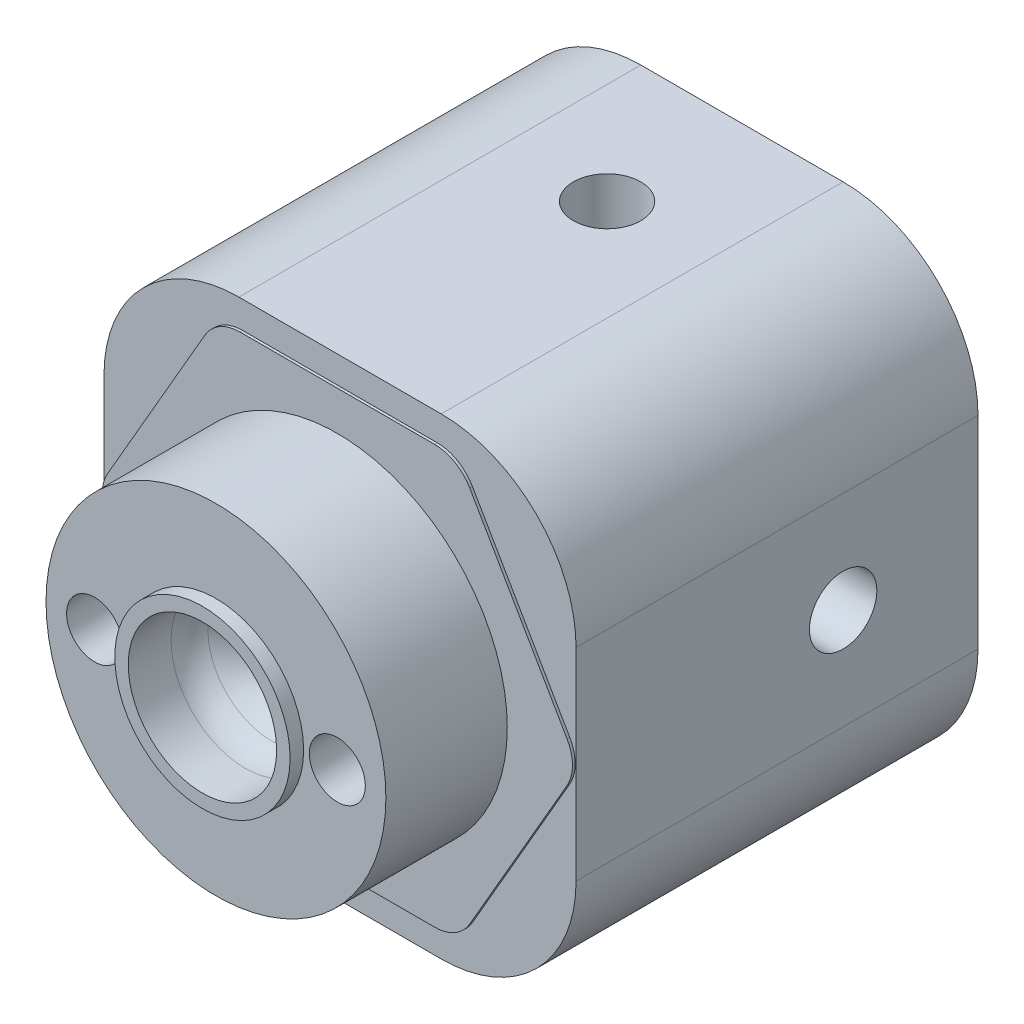
SolidWorks part; units mm, degrees
ref_plane "前视基准面" through (0, 0, 0) normal (0, 0, 1) x (1, 0, 0)
ref_plane "上视基准面" through (0, 0, 0) normal (0, 1, 0) x (1, 0, 0)
ref_plane "右视基准面" through (0, 0, 0) normal (1, 0, 0) x (0, 0, -1)
sketch "草图1" plane through (0, 0, 0) normal (0, 0, 1) x (1, 0, 0)
  circle A0 centre (0, 0) radius 12.6
  dimension "D1" = 25.2
extrude "凸台-拉伸1" add sketch "草图1" along normal blind 9
sketch "草图2" plane through (0, 0, 0) normal (0, 0, -1) x (-1, 0, 0)
  circle A0 centre (0, 0) radius 15
  dimension "D1" = 30
extrude "凸台-拉伸2" add sketch "草图2" along normal blind 5
sketch "草图3" plane through (0, 0, 9) normal (0, 0, 1) x (1, 0, 0)
  circle A0 centre (0, 0) radius 5.5
  dimension "D1" = 11
extrude "切除-拉伸1" cut sketch "草图3" against normal blind 5
sketch "草图4" plane through (0, 0, 9) normal (0, 0, 1) x (1, 0, 0)
  circle A0 centre (-9, 0) radius 2.075
  circle A1 centre (9, 0) radius 2.075
  dimension "D1" = 4.15
  dimension "D2" = 9
  dimension "D3" = 9
extrude "切除-拉伸2" cut sketch "草图4" against normal blind 29
sketch "草图5" plane through (0, 0, 4) normal (0, 0, 1) x (1, 0, 0)
  circle A0 centre (0, 0) radius 3.5
  dimension "D1" = 7
extrude "切除-拉伸3" cut sketch "草图5" against normal blind 31
fillet "圆角1" radius 3 1 edges at (5.5, 0, 4)
fillet "圆角2" radius 5 1 edges at (3.5, 0, 4)
sketch "草图6" plane through (0, 0, 9) normal (0, 0, 1) x (1, 0, 0)
  circle A0 centre (0, 0) radius 5.5
  dimension "D1" = 11
extrude "拉伸-薄壁1" add sketch "草图6" along normal blind 1 thin thin type one direction wall 1
sketch "草图7" plane through (0, 0, -5) normal (0, 0, -1) x (-1, 0, 0)
  line L1 (-8.9489, 15.5) -> (-17.8979, 0)
  line L2 (-17.8979, 0) -> (-8.9489, -15.5)
  line L3 (-8.9489, -15.5) -> (8.9489, -15.5)
  line L4 (8.9489, -15.5) -> (17.8979, 0)
  line L5 (17.8979, 0) -> (8.9489, 15.5)
  line L6 (8.9489, 15.5) -> (-8.9489, 15.5)
  circle A0 centre (0, 0) radius 15.5 construction
  circle A1 centre (0, 0) radius 15
  circle A2 centre (0, 0) radius 15
  dimension "D2" = 31
  dimension "D1" = 0
extrude "凸台-拉伸3" add sketch "草图7" against normal up to surface (5 mm away) up to face at (12.6, 0, 0)
fillet "圆角3" radius 3 6 edges at (17.8979, 0, -2.5) (8.9489, 15.5, -2.5) (-8.9489, 15.5, -2.5) (-17.8979, 0, -2.5) (-8.9489, -15.5, -2.5) (8.9489, -15.5, -2.5)
sketch "草图8" plane through (0, 0, -5) normal (0, 0, -1) x (-1, 0, 0)
  line L6 (-9.815, 14) -> (-17.0318, 1.5)
  line L7 (-17.0318, -1.5) -> (-9.815, -14)
  line L8 (-7.2169, -15.5) -> (7.2169, -15.5)
  line L9 (9.815, -14) -> (17.0318, -1.5)
  line L10 (17.0318, 1.5) -> (9.815, 14)
  line L11 (7.2169, 15.5) -> (-7.2169, 15.5)
  line L12 (-9.815, 14) -> (-17.0318, 1.5)
  line L13 (-17.0318, -1.5) -> (-9.815, -14)
  line L14 (-7.2169, -15.5) -> (7.2169, -15.5)
  line L15 (9.815, -14) -> (17.0318, -1.5)
  line L16 (17.0318, 1.5) -> (9.815, 14)
  line L17 (7.2169, 15.5) -> (-7.2169, 15.5)
  circle A0 centre (0, 0) radius 3.5 construction
  circle A1 centre (0, 0) radius 3.5
  circle A2 centre (-9, 0) radius 4
  circle A3 centre (9, 0) radius 4
  arc A6 (-17.0318, 1.5) -> (-17.0318, -1.5) centre (-14.4338, 0) ccw
  arc A7 (-9.815, -14) -> (-7.2169, -15.5) centre (-7.2169, -12.5) ccw
  arc A8 (7.2169, -15.5) -> (9.815, -14) centre (7.2169, -12.5) ccw
  arc A9 (17.0318, -1.5) -> (17.0318, 1.5) centre (14.4338, 0) ccw
  arc A10 (9.815, 14) -> (7.2169, 15.5) centre (7.2169, 12.5) ccw
  arc A11 (-7.2169, 15.5) -> (-9.815, 14) centre (-7.2169, 12.5) ccw
  arc A12 (-17.0318, 1.5) -> (-17.0318, -1.5) centre (-14.4338, 0) ccw
  arc A13 (-9.815, -14) -> (-7.2169, -15.5) centre (-7.2169, -12.5) ccw
  arc A14 (7.2169, -15.5) -> (9.815, -14) centre (7.2169, -12.5) ccw
  arc A15 (17.0318, -1.5) -> (17.0318, 1.5) centre (14.4338, 0) ccw
  arc A16 (9.815, 14) -> (7.2169, 15.5) centre (7.2169, 12.5) ccw
  arc A17 (-7.2169, 15.5) -> (-9.815, 14) centre (-7.2169, 12.5) ccw
  dimension "D2" = 8
  dimension "D3" = 8
  dimension "D1" = 0
extrude "凸台-拉伸4" add sketch "草图8" along normal blind 5
sketch "草图9" plane through (0, 0, -10) normal (0, 0, -1) x (-1, 0, 0)
  line L1 (-10.05, 10.05) -> (10.05, 10.05)
  line L2 (-10.05, 10.05) -> (-10.05, -10.05)
  line L3 (-10.05, -10.05) -> (10.05, -10.05)
  line L4 (10.05, 10.05) -> (10.05, -10.05)
  line L5 (-10.05, 10.05) -> (10.05, -10.05) construction
  line L6 (-10.05, -10.05) -> (10.05, 10.05) construction
  line L7 (17.5, -17.5) -> (-17.5, -17.5)
  line L8 (17.5, -17.5) -> (17.5, 17.5)
  line L9 (17.5, 17.5) -> (-17.5, 17.5)
  line L10 (-17.5, -17.5) -> (-17.5, 17.5)
  line L11 (17.5, -17.5) -> (-17.5, 17.5) construction
  line L12 (17.5, 17.5) -> (-17.5, -17.5) construction
  point P0 (0, 0)
  point P6 (0, 0)
  dimension "D1" = 20.1
  dimension "D2" = 20.1
  dimension "D3" = 35
  dimension "D4" = 35
extrude "凸台-拉伸5" add sketch "草图9" along normal blind 20
sketch "草图10" plane through (0, 0, -10) normal (0, 0, 1) x (1, 0, 0)
  line L4 (17.5, -17.5) -> (17.5, 17.5)
  line L5 (17.5, 17.5) -> (-17.5, 17.5)
  line L6 (-17.5, 17.5) -> (-17.5, -17.5)
  line L7 (-17.5, -17.5) -> (17.5, -17.5)
  line L8 (17.5, -17.5) -> (17.5, 17.5)
  line L9 (17.5, 17.5) -> (-17.5, 17.5)
  line L10 (-17.5, 17.5) -> (-17.5, -17.5)
  line L11 (-17.5, -17.5) -> (17.5, -17.5)
  line L14 (7.2169, 15.5) -> (-7.2169, 15.5)
  line L15 (17.0318, 1.5) -> (9.815, 14)
  line L16 (9.815, -14) -> (17.0318, -1.5)
  line L17 (-7.2169, -15.5) -> (7.2169, -15.5)
  line L18 (-17.0318, -1.5) -> (-9.815, -14)
  line L19 (-9.815, 14) -> (-17.0318, 1.5)
  line L20 (7.2169, 15.5) -> (-7.2169, 15.5)
  line L21 (17.0318, 1.5) -> (9.815, 14)
  line L22 (9.815, -14) -> (17.0318, -1.5)
  line L23 (-7.2169, -15.5) -> (7.2169, -15.5)
  line L24 (-17.0318, -1.5) -> (-9.815, -14)
  line L25 (-9.815, 14) -> (-17.0318, 1.5)
  arc A6 (9.815, 14) -> (7.2169, 15.5) centre (7.2169, 12.5) ccw
  arc A7 (17.0318, -1.5) -> (17.0318, 1.5) centre (14.4338, 0) ccw
  arc A8 (7.2169, -15.5) -> (9.815, -14) centre (7.2169, -12.5) ccw
  arc A9 (-9.815, -14) -> (-7.2169, -15.5) centre (-7.2169, -12.5) ccw
  arc A10 (-17.0318, 1.5) -> (-17.0318, -1.5) centre (-14.4338, 0) ccw
  arc A11 (-7.2169, 15.5) -> (-9.815, 14) centre (-7.2169, 12.5) ccw
  arc A12 (9.815, 14) -> (7.2169, 15.5) centre (7.2169, 12.5) ccw
  arc A13 (17.0318, -1.5) -> (17.0318, 1.5) centre (14.4338, 0) ccw
  arc A14 (7.2169, -15.5) -> (9.815, -14) centre (7.2169, -12.5) ccw
  arc A15 (-9.815, -14) -> (-7.2169, -15.5) centre (-7.2169, -12.5) ccw
  arc A16 (-17.0318, 1.5) -> (-17.0318, -1.5) centre (-14.4338, 0) ccw
  arc A17 (-7.2169, 15.5) -> (-9.815, 14) centre (-7.2169, 12.5) ccw
  dimension "D1" = 0
  dimension "D2" = 0
extrude "凸台-拉伸6" add sketch "草图10" along normal blind 8.5
fillet "圆角4" radius 10 4 edges at (-17.5, 17.5, -15.75) (-17.5, -17.5, -15.75) (17.5, -17.5, -15.75) (17.5, 17.5, -15.75)
sketch "草图11" plane through (-17.5, 0, 0) normal (-1, 0, 0) x (0, 0, 1)
  line L0 (-30, -7.5) -> (-30, 7.5) construction
  circle A0 centre (-20, 0) radius 2.5
  dimension "D1" = 5
  dimension "D2" = 10
extrude "切除-拉伸4" cut sketch "草图11" against normal blind 15
pattern_circular "阵列(圆周)1" count 4 over 360 about axis through (0, 0, -27) along (0, 0, 1) of "切除-拉伸4"
sketch "草图12" plane through (0, 0, -5) normal (0, 0, -1) x (-1, 0, 0)
  circle A1 centre (9, 0) radius 4
  circle A2 centre (9, 0) radius 4
  circle A3 centre (-9, 0) radius 4
  circle A4 centre (-9, 0) radius 4
  dimension "D1" = 0
  dimension "D2" = 0
extrude "切除-拉伸5" cut sketch "草图12" along normal blind 83
sketch "草图13" plane through (0, 0, -10) normal (0, 0, -1) x (-1, 0, 0)
  line L0 (0, 3.5) -> (0, 10.05)
  line L1 (10.05, 10.05) -> (-10.05, 10.05) construction
  line L2 (0, 0) -> (0, 3.5)
  circle A0 centre (0, 0) radius 3.5 construction
extrude "切除-拉伸-薄壁1" [suppressed] cut sketch "草图13" against normal blind 4 thin thin type mid plane wall 4
fillet "圆角5" [suppressed] radius 4
fillet "圆角6" [suppressed] radius 4
fillet "圆角7" [suppressed] radius 3
sketch "草图14" plane through (0, 0, -1.5) normal (0, 0, 1) x (1, 0, 0)
  line L4 (7.5, 17.5) -> (-7.5, 17.5)
  line L5 (-17.5, 7.5) -> (-17.5, -7.5)
  line L6 (-7.5, -17.5) -> (7.5, -17.5)
  line L7 (17.5, -7.5) -> (17.5, 7.5)
  line L8 (7.5, 17.5) -> (-7.5, 17.5)
  line L9 (-17.5, 7.5) -> (-17.5, -7.5)
  line L10 (-7.5, -17.5) -> (7.5, -17.5)
  line L11 (17.5, -7.5) -> (17.5, 7.5)
  line L14 (9.815, -14) -> (17.0318, -1.5)
  line L15 (17.0318, 1.5) -> (9.815, 14)
  line L16 (7.2169, 15.5) -> (-7.2169, 15.5)
  line L17 (-9.815, 14) -> (-17.0318, 1.5)
  line L18 (-17.0318, -1.5) -> (-9.815, -14)
  line L19 (-7.2169, -15.5) -> (7.2169, -15.5)
  line L20 (9.815, -14) -> (17.0318, -1.5)
  line L21 (17.0318, 1.5) -> (9.815, 14)
  line L22 (7.2169, 15.5) -> (-7.2169, 15.5)
  line L23 (-9.815, 14) -> (-17.0318, 1.5)
  line L24 (-17.0318, -1.5) -> (-9.815, -14)
  line L25 (-7.2169, -15.5) -> (7.2169, -15.5)
  arc A4 (-7.5, 17.5) -> (-17.5, 7.5) centre (-7.5, 7.5) ccw
  arc A5 (-17.5, -7.5) -> (-7.5, -17.5) centre (-7.5, -7.5) ccw
  arc A6 (7.5, -17.5) -> (17.5, -7.5) centre (7.5, -7.5) ccw
  arc A7 (17.5, 7.5) -> (7.5, 17.5) centre (7.5, 7.5) ccw
  arc A8 (-7.5, 17.5) -> (-17.5, 7.5) centre (-7.5, 7.5) ccw
  arc A9 (-17.5, -7.5) -> (-7.5, -17.5) centre (-7.5, -7.5) ccw
  arc A10 (7.5, -17.5) -> (17.5, -7.5) centre (7.5, -7.5) ccw
  arc A11 (17.5, 7.5) -> (7.5, 17.5) centre (7.5, 7.5) ccw
  arc A14 (17.0318, -1.5) -> (17.0318, 1.5) centre (14.4338, 0) ccw
  arc A15 (9.815, 14) -> (7.2169, 15.5) centre (7.2169, 12.5) ccw
  arc A16 (-7.2169, 15.5) -> (-9.815, 14) centre (-7.2169, 12.5) ccw
  arc A17 (-17.0318, 1.5) -> (-17.0318, -1.5) centre (-14.4338, 0) ccw
  arc A18 (-9.815, -14) -> (-7.2169, -15.5) centre (-7.2169, -12.5) ccw
  arc A19 (7.2169, -15.5) -> (9.815, -14) centre (7.2169, -12.5) ccw
  arc A20 (17.0318, -1.5) -> (17.0318, 1.5) centre (14.4338, 0) ccw
  arc A21 (9.815, 14) -> (7.2169, 15.5) centre (7.2169, 12.5) ccw
  arc A22 (-7.2169, 15.5) -> (-9.815, 14) centre (-7.2169, 12.5) ccw
  arc A23 (-17.0318, 1.5) -> (-17.0318, -1.5) centre (-14.4338, 0) ccw
  arc A24 (-9.815, -14) -> (-7.2169, -15.5) centre (-7.2169, -12.5) ccw
  arc A25 (7.2169, -15.5) -> (9.815, -14) centre (7.2169, -12.5) ccw
  dimension "D1" = 0
  dimension "D2" = 0
extrude "凸台-拉伸7" add sketch "草图14" along normal blind 1.3
